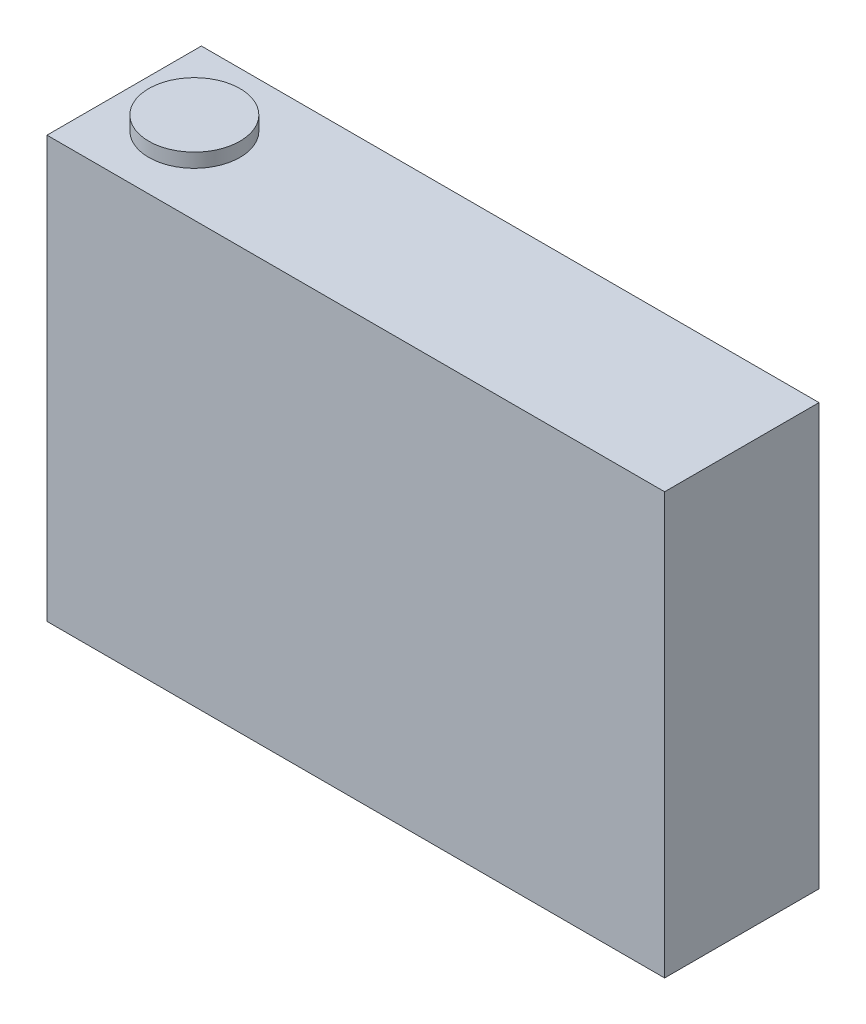
SolidWorks part; units mm, degrees
ref_plane "Front Plane" through (0, 0, 0) normal (0, 0, 1) x (1, 0, 0)
ref_plane "Top Plane" through (0, 0, 0) normal (0, 1, 0) x (1, 0, 0)
ref_plane "Right Plane" through (0, 0, 0) normal (1, 0, 0) x (0, 0, -1)
sketch "Sketch1" plane through (0, 0, 0) normal (0, 1, 0) x (1, 0, 0)
  line L1 (-44, -11) -> (44, -11)
  line L2 (-44, -11) -> (-44, 11)
  line L3 (-44, 11) -> (44, 11)
  line L4 (44, -11) -> (44, 11)
  line L5 (-44, -11) -> (44, 11) construction
  line L6 (-44, 11) -> (44, -11) construction
  circle A0 centre (-34, 0) radius 6.5
  point P0 (0, 0)
  dimension "D3" = 13
  dimension "D1" = 88
  dimension "D2" = 22
  dimension "D4" = 10
  dimension "D5" = 11
extrude "Boss-Extrude1" add sketch "Sketch1" along normal blind 60
extrude "Boss-Extrude2" add sketch "Sketch1<3>" along normal blind 62 contours A0
sketch "Sketch1<3>" plane through (0, 0, 0) normal (0, 1, 0) x (1, 0, 0) same geometry as "Sketch1"
